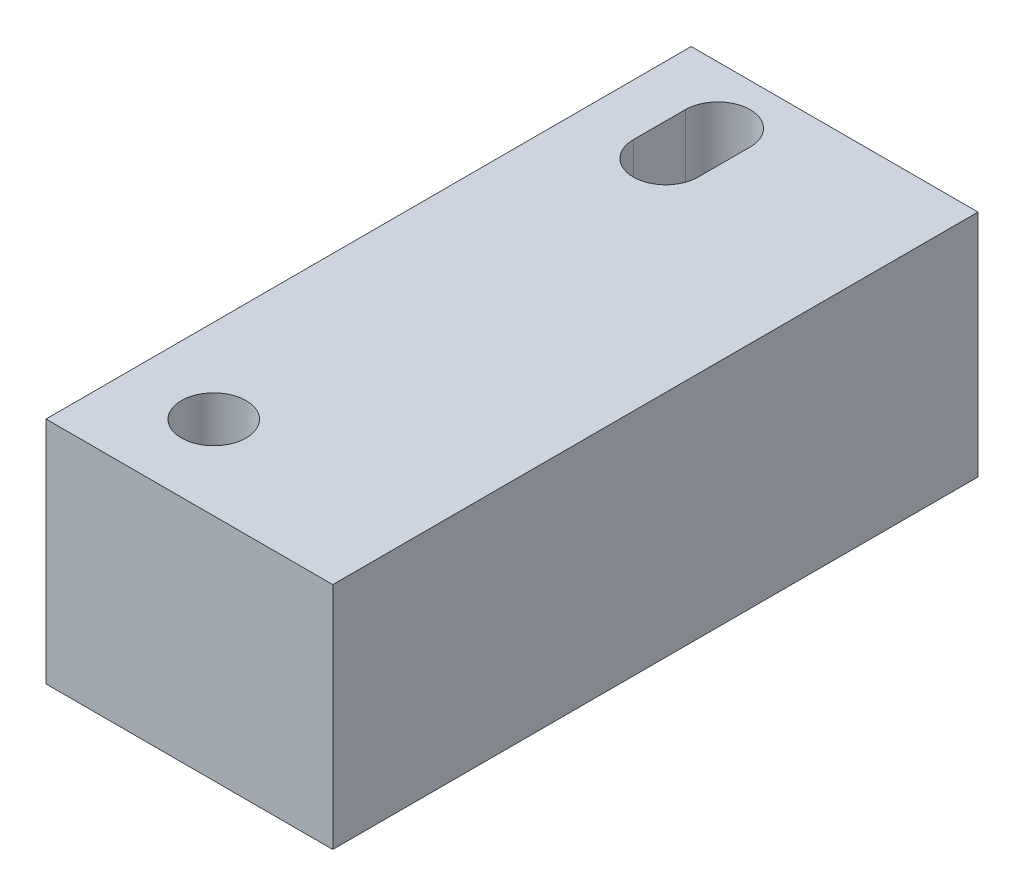
SolidWorks part; units mm, degrees
ref_plane "Front Plane" through (0, 0, 0) normal (0, 0, 1) x (1, 0, 0)
ref_plane "Top Plane" through (0, 0, 0) normal (0, 1, 0) x (1, 0, 0)
ref_plane "Right Plane" through (0, 0, 0) normal (1, 0, 0) x (0, 0, -1)
sketch "Sketch1" plane through (0, 0, 0) normal (0, 1, 0) x (1, 0, 0)
  line L1 (-25.7386, -23.0293) -> (-6.6886, -23.0293)
  line L2 (-25.7386, -23.0293) -> (-25.7386, 19.8332)
  line L3 (-25.7386, 19.8332) -> (-6.6886, 19.8332)
  line L4 (-6.6886, -23.0293) -> (-6.6886, 19.8332)
  dimension "D1" = 42.8625
  dimension "D2" = 19.05
extrude "Boss-Extrude1" add sketch "Sketch1" along normal blind 15.24
sketch "Sketch4" plane through (0, 15.24, 0) normal (0, 1, 0) x (1, 0, 0)
  line L0 (-20.1506, 16.0042) -> (-20.1506, 12.5498) construction
  line L1 (-17.9979, 16.0042) -> (-17.9979, 12.5498)
  line L2 (-22.3032, 16.0042) -> (-22.3032, 12.5498)
  line L3 (-25.7386, 19.8332) -> (-25.7386, -23.0293) construction
  arc A1 (-17.9979, 16.0042) -> (-22.3032, 16.0042) centre (-20.1506, 16.0042) ccw
  arc A2 (-22.3032, 12.5498) -> (-17.9979, 12.5498) centre (-20.1506, 12.5498) ccw
  point P5 (-20.1506, 14.277)
  dimension "D2" = 3.4544
  dimension "D1" = 4.3053
  dimension "D3" = 5.588
hole_wizard "#18 (0.1695) Diameter Hole1" positions "Sketch6" profile "Sketch5" hole size "#18" standard "Ansi Inch" end condition up to next
sketch "Sketch6" plane through (0, 15.24, 0) normal (0, 1, 0) x (-1, 0, 0)
  line L0 (25.7386, -19.8332) -> (25.7386, 23.0293) construction
  point P0 (20.1506, 17.473)
  dimension "D1" = 31.75
  dimension "D2" = 5.588
sketch "Sketch5" plane through (-20.1506, 15.24, 17.473) normal (1, 0, 0) x (0, 0, 1)
  line L0 (0, 0) -> (0, 15.24)
  line L1 (0, 15.24) -> (2.1526, 15.24)
  line L2 (2.1526, 15.24) -> (2.1526, 0)
  line L5 (2.1526, 0) -> (0, 0)
  line L11 (0, -6.35) -> (0, 107.95) construction
  dimension "Thru Hole Dia." = 4.3053
  dimension "Thru Hole Depth" = 15.24
extrude "Cut-Extrude1" cut sketch "Sketch4" against normal up to next
ref_axis "Axis1" through (-20.1506, 15.24, -10.3971) along (0, 0, -1)
ref_axis "Axis2" through (-17.9979, 15.24, -14.277) along (-1, 0, 0)
ref_plane "Plane1" through (-20.1506, 0, 0) normal (-1, 0, 0) x (0, 0, 1)
ref_plane "Plane2" through (0, 0, -14.277) normal (0, 0, -1) x (-1, 0, 0)
ref_axis "Axis3" through (-20.1506, 23.3877, -14.277) along (0, -1, 0)
equation "\"D2@Sketch6\" = \"D3@Sketch4\""
